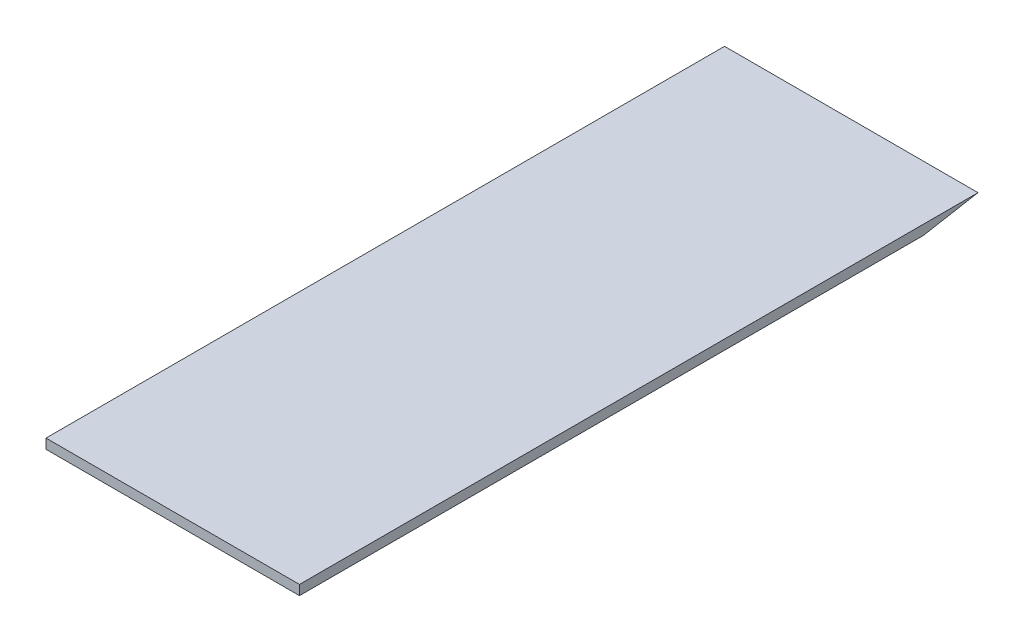
SolidWorks part; units mm, degrees
ref_plane "Front Plane" through (0, 0, 0) normal (0, 0, 1) x (1, 0, 0)
ref_plane "Top Plane" through (0, 0, 0) normal (0, 1, 0) x (1, 0, 0)
ref_plane "Right Plane" through (0, 0, 0) normal (1, 0, 0) x (0, 0, -1)
sketch "Sketch1" plane through (0, 0, 0) normal (1, 0, 0) x (0, 0, -1)
  line L19 (0, 5) -> (0, 0)
  line L20 (0, 0) -> (320, 0)
  line L21 (320, 0) -> (348, 5)
  line L37 (0, 5) -> (348, 5)
  dimension "D1" = 5
  dimension "D8" = 28
  dimension "D9" = 320
extrude "Boss-Extrude1" add sketch "Sketch1" along normal blind 130 contours L19 L20 L21 L37
